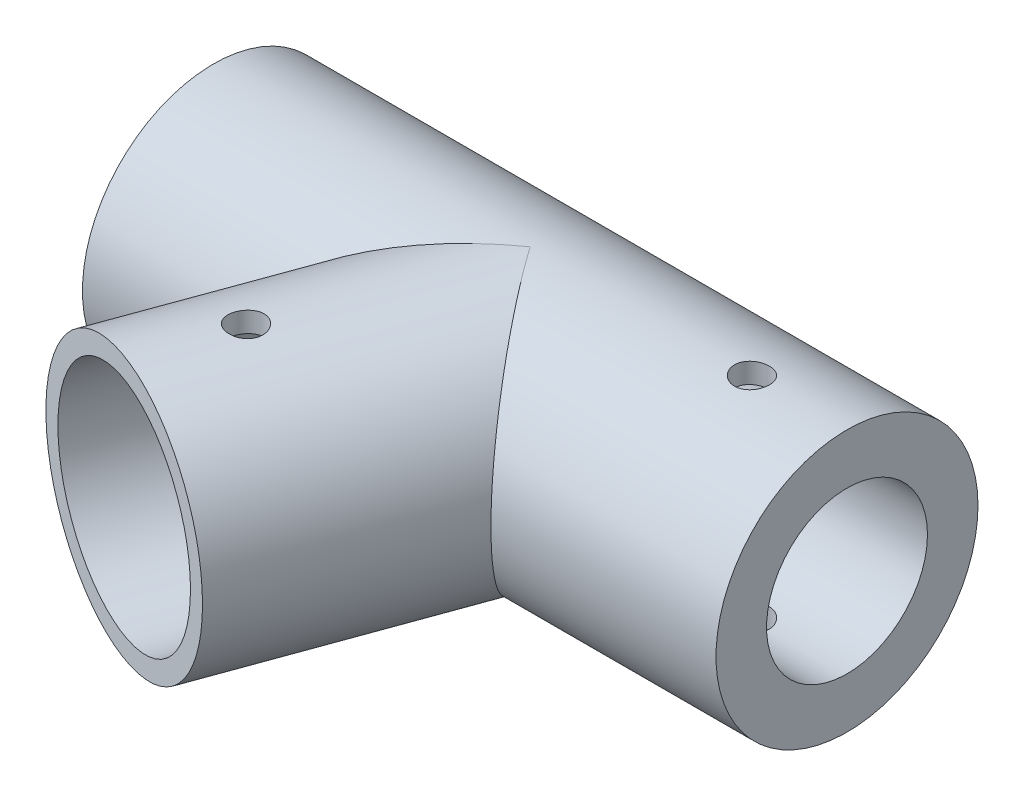
SolidWorks part; units mm, degrees
material "1060 Alloy"
ref_plane "Front Plane" through (0, 0, 0) normal (0, 0, 1) x (1, 0, 0)
ref_plane "Top Plane" through (0, 0, 0) normal (0, 1, 0) x (1, 0, 0)
ref_plane "Right Plane" through (0, 0, 0) normal (1, 0, 0) x (0, 0, -1)
sketch "Sketch1" plane through (0, 0, 0) normal (0, 1, 0) x (1, 0, 0)
  line L0 (0, 0) -> (100, 0) construction
  line L1 (50, 0) -> (32.899, -46.9846) construction
  dimension "D1" = 100
  dimension "D2" = 50
  dimension "D3" = 70
ref_plane "Plane1" through (0, 0, 0) normal (1, 0, 0) x (0, 0, -1)
sketch "Sketch2" plane through (0, 0, 0) normal (1, 0, 0) x (0, 0, -1)
  circle A0 centre (0, 0) radius 20.675
  dimension "D1" = 41.35
extrude "Boss-Extrude1" add sketch "Sketch2" along normal up to vertex (100 mm away) up to point (100, 0, 0)
ref_plane "Plane2" through (32.899, 0, 46.9846) normal (-0.342, 0, 0.9397) x (0.9397, 0, 0.342)
sketch "Sketch3" plane through (32.899, 0, 46.9846) normal (-0.342, 0, 0.9397) x (0.9397, 0, 0.342)
  line L0 (-46.9846, 0) -> (46.9846, 0) construction
  circle A0 centre (0, 0) radius 20.675
  dimension "D1" = 41.35
extrude "Boss-Extrude2" add sketch "Sketch3" against normal up to surface (35.5232 mm away) up to face at (100, 0, -20.675)
sketch "Sketch4" plane through (100, 0, 0) normal (1, 0, 0) x (0, 0, -1)
  circle A0 centre (0, 0) radius 12.7
  dimension "D1" = 25.4
extrude "Cut-Extrude1" cut sketch "Sketch4" against normal through all
shell "Shell1" thickness 3.175 removed face at (52.3271, 0, 54.0559)
sketch "Sketch5" plane through (0, 0, 0) normal (0, 1, 0) x (1, 0, 0)
  line L0 (100, 0) -> (85, 0) construction
  line L1 (100, -20.675) -> (100, 20.675) construction
  line L2 (32.899, -46.9846) -> (38.0293, -32.8892) construction
  line L3 (13.4708, -39.9134) -> (52.3271, -54.0559) construction
  dimension "D1" = 90
  dimension "D2" = 15
  dimension "D3" = 15
hole_wizard "M5 Clearance Hole1" positions "Sketch6" profile "Sketch7" hole size "M5" standard "AS" end condition through all
sketch "Sketch6" plane through (0, 0, 0) normal (0, 1, 0) x (1, 0, 0)
  point P0 (85, 0)
  point P3 (38.0293, -32.8892)
sketch "Sketch7" plane through (85, 0, 0) normal (1, 0, 0) x (0, 0, -1)
  line L0 (0, 0) -> (0, 20.675)
  line L1 (0, 20.675) -> (2.75, 20.675)
  line L2 (2.75, 20.675) -> (2.75, 0)
  line L5 (2.75, 0) -> (0, 0)
  line L11 (0, -6.35) -> (0, 107.95) construction
  dimension "Thru Hole Dia." = 5.5
  dimension "Thru Hole Depth" = 20.675
mirror "Mirror1" about plane through (0, 0, 0) normal (0, 1, 0) of "M5 Clearance Hole1"
equation "\"frontTubeLength\"= 1200mm"
equation "\"outDiameter\"= 35mm"
equation "\"keelOutDiameter\"= 1in"
equation "\"D1@Sketch2\"=\"outDiameter\"+0.25in"
equation "\"D1@Sketch3\"=\"outDiameter\"+0.25in"
equation "\"D1@Sketch4\"=\"keelOutDiameter\""
